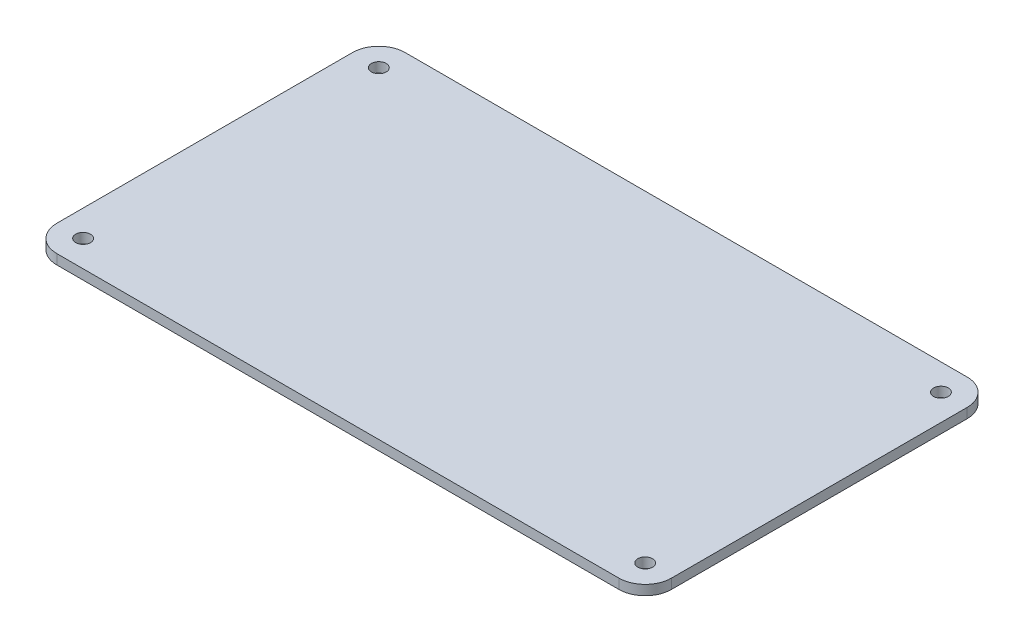
SolidWorks part; units mm, degrees
ref_plane "Front Plane" through (0, 0, 0) normal (0, 0, 1) x (1, 0, 0)
ref_plane "Top Plane" through (0, 0, 0) normal (0, 1, 0) x (1, 0, 0)
ref_plane "Right Plane" through (0, 0, 0) normal (1, 0, 0) x (0, 0, -1)
sketch "Sketch2" plane through (0, 0, 0) normal (0, 1, 0) x (1, 0, 0)
  line L0 (-12.7, 0) -> (-12.7, -142.8826)
  line L1 (0, 0) -> (271.587, 0) construction
  line L2 (0, 0) -> (0, -142.8826) construction
  line L3 (0, -142.8826) -> (271.587, -142.8826) construction
  line L4 (271.587, 0) -> (271.587, -142.8826) construction
  line L9 (0, -155.5826) -> (271.587, -155.5826)
  line L10 (284.287, -142.8826) -> (284.287, 0)
  line L11 (271.587, 12.7) -> (0, 12.7)
  arc A0 (0, 12.7) -> (-12.7, 0) centre (0, 0) ccw
  arc A1 (-12.7, -142.8826) -> (0, -155.5826) centre (0, -142.8826) ccw
  arc A2 (271.587, -155.5826) -> (284.287, -142.8826) centre (271.587, -142.8826) ccw
  arc A3 (271.587, 12.7) -> (284.287, 0) centre (271.587, 0) cw
  dimension "D3" = 12.7
  dimension "D1" = 271.587
  dimension "D2" = 142.8826
extrude "Boss-Extrude1" add sketch "Sketch2" along normal blind 4.7625
hole_wizard "1/4 Clearance Hole1" positions "Sketch3" profile "Sketch4" hole size "1/4" standard "ANSI Inch" end condition through all
sketch "Sketch3" plane through (0, 4.7625, 0) normal (0, 1, 0) x (1, 0, 0)
  point P0 (0, 0)
  point P3 (0, -142.8826)
  point P6 (271.587, -142.8826)
  point P9 (271.587, 0)
sketch "Sketch4" plane through (0, 4.7625, 0) normal (1, 0, 0) x (0, 0, 1)
  line L0 (0, 0) -> (0, 4.7625)
  line L1 (0, 4.7625) -> (3.5712, 4.7625)
  line L2 (3.5712, 4.7625) -> (3.5712, 0)
  line L5 (3.5712, 0) -> (0, 0)
  line L11 (0, -6.35) -> (0, 107.95) construction
  dimension "Thru Hole Dia." = 7.1425
  dimension "Thru Hole Depth" = 4.7625
